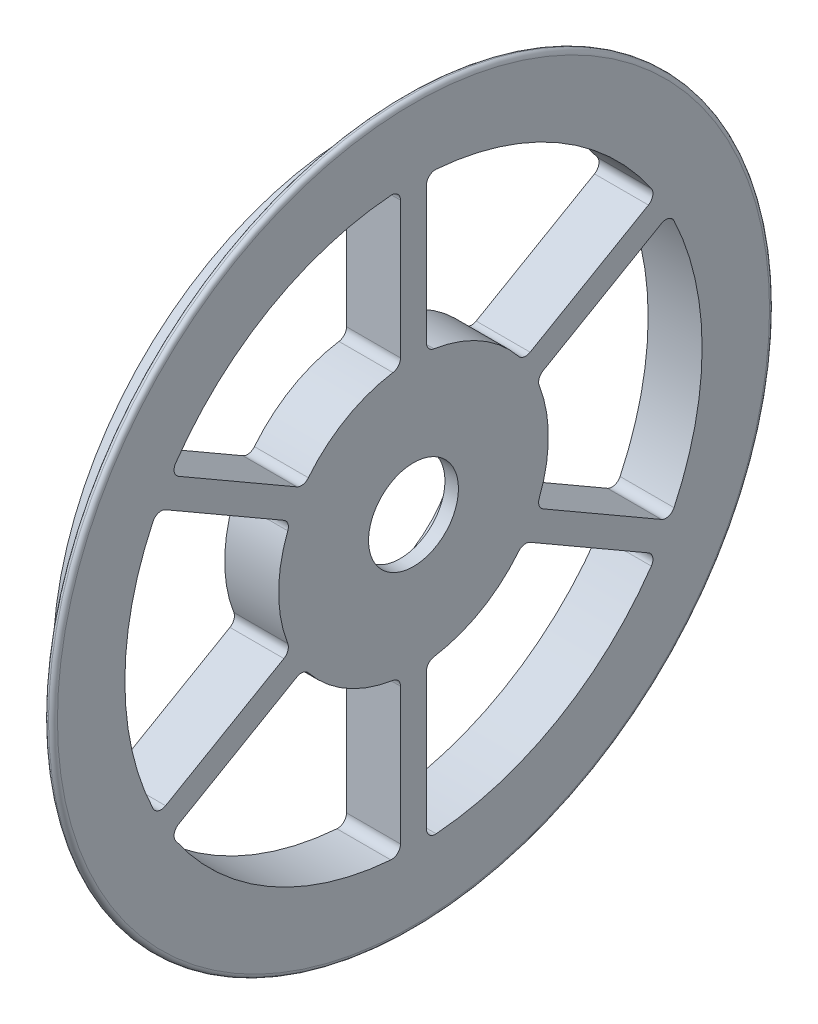
SolidWorks part; units mm, degrees
ref_plane "Front Plane" through (0, 0, 0) normal (0, 0, 1) x (1, 0, 0)
ref_plane "Top Plane" through (0, 0, 0) normal (0, 1, 0) x (1, 0, 0)
ref_plane "Right Plane" through (0, 0, 0) normal (1, 0, 0) x (0, 0, -1)
sketch "Sketch1" plane through (0, 0, 0) normal (0, 0, 1) x (1, 0, 0)
  line L2 (-3, 0) -> (-3, 38.05)
  line L5 (-3, 38.05) -> (2, 38.05)
  line L14 (2, 38.05) -> (2, 40.1)
  line L15 (2, 40.1) -> (3, 40.1)
  line L16 (3, 40.1) -> (3, 0)
  line L17 (3, 0) -> (-3, 0)
  dimension "D3" = 40.1
  dimension "D1" = 1
  dimension "D2" = 5
  dimension "D4" = 38.05
revolve "Revolve2" add sketch "Sketch1" angle 360 about L17
sketch "Sketch2" plane through (3, 0, 0) normal (-1, 0, 0) x (0, 0, 1)
  line L0 (0, 0) -> (13.6518, 0) construction
  line L1 (14.4156, 6.6562) -> (27.5718, 14.2519)
  line L2 (13.6518, 6.2152) -> (13.6518, -6.2152) construction
  line L3 (14.4156, -6.6562) -> (27.5718, -14.2519)
  line L4 (28.493, 14.7838) -> (28.493, -14.7838) construction
  line L5 (2.8868, 0) -> (13.6518, 6.2152) construction
  line L6 (2.8868, 0) -> (1.4434, 2.5) construction
  line L7 (1.4434, 2.5) -> (-1.4434, 2.5) construction
  line L8 (-1.4434, 2.5) -> (-2.8868, 0) construction
  line L9 (-2.8868, 0) -> (-1.4434, -2.5) construction
  line L10 (-1.4434, -2.5) -> (1.4434, -2.5) construction
  line L11 (1.4434, -2.5) -> (2.8868, 0) construction
  line L12 (13.6518, 0) -> (28.493, 0) construction
  line L13 (13.6518, -6.2152) -> (2.8868, 0) construction
  line L14 (12.9722, -9.1562) -> (26.1285, -16.7519)
  line L15 (1.4434, -15.8123) -> (1.4434, -31.0039)
  line L16 (-1.4434, -15.8123) -> (-1.4434, -31.0039)
  line L17 (-12.9722, -9.1562) -> (-26.1285, -16.7519)
  line L18 (-14.4156, -6.6562) -> (-27.5718, -14.2519)
  line L19 (-14.4156, 6.6562) -> (-27.5718, 14.2519)
  line L20 (-12.9722, 9.1562) -> (-26.1285, 16.7519)
  line L21 (-1.4434, 15.8123) -> (-1.4434, 31.0039)
  line L22 (1.4434, 15.8123) -> (1.4434, 31.0039)
  line L23 (12.9722, 9.1562) -> (26.1285, 16.7519)
  arc A0 (28.9745, 13.8163) -> (28.9745, -13.8163) centre (0, 0) cw
  circle A2 centre (0, 0) radius 2.5 construction
  arc A3 (13.9833, 5.4283) -> (13.9833, -5.4283) centre (0, 0) cw
  arc A4 (13.9833, -5.4283) -> (14.4156, -6.6562) centre (14.9156, -5.7901) ccw
  arc A5 (14.4156, 6.6562) -> (13.9833, 5.4283) centre (14.9156, 5.7901) ccw
  arc A6 (27.5718, -14.2519) -> (28.9745, -13.8163) centre (28.0718, -13.3859) ccw
  arc A7 (28.9745, 13.8163) -> (27.5718, 14.2519) centre (28.0718, 13.3859) ccw
  arc A8 (26.4525, -18.1845) -> (26.1285, -16.7519) centre (25.6285, -17.618) ccw
  arc A9 (26.4525, -18.1845) -> (2.5219, -32.0008) centre (0, 0) cw
  arc A10 (1.4434, -31.0039) -> (2.5219, -32.0008) centre (2.4434, -31.0039) ccw
  arc A11 (2.2907, -14.8241) -> (1.4434, -15.8123) centre (2.4434, -15.8123) ccw
  arc A12 (11.6927, -9.3958) -> (2.2907, -14.8241) centre (0, 0) cw
  arc A13 (12.9722, -9.1562) -> (11.6927, -9.3958) centre (12.4722, -10.0222) ccw
  arc A14 (-2.5219, -32.0008) -> (-1.4434, -31.0039) centre (-2.4434, -31.0039) ccw
  arc A15 (-2.5219, -32.0008) -> (-26.4525, -18.1845) centre (0, 0) cw
  arc A16 (-26.1285, -16.7519) -> (-26.4525, -18.1845) centre (-25.6285, -17.618) ccw
  arc A17 (-11.6927, -9.3958) -> (-12.9722, -9.1562) centre (-12.4722, -10.0222) ccw
  arc A18 (-2.2907, -14.8241) -> (-11.6927, -9.3958) centre (0, 0) cw
  arc A19 (-1.4434, -15.8123) -> (-2.2907, -14.8241) centre (-2.4434, -15.8123) ccw
  arc A20 (-28.9745, -13.8163) -> (-27.5718, -14.2519) centre (-28.0718, -13.3859) ccw
  arc A21 (-28.9745, -13.8163) -> (-28.9745, 13.8163) centre (0, 0) cw
  arc A22 (-27.5718, 14.2519) -> (-28.9745, 13.8163) centre (-28.0718, 13.3859) ccw
  arc A23 (-13.9833, 5.4283) -> (-14.4156, 6.6562) centre (-14.9156, 5.7901) ccw
  arc A24 (-13.9833, -5.4283) -> (-13.9833, 5.4283) centre (0, 0) cw
  arc A25 (-14.4156, -6.6562) -> (-13.9833, -5.4283) centre (-14.9156, -5.7901) ccw
  arc A26 (-26.4525, 18.1845) -> (-26.1285, 16.7519) centre (-25.6285, 17.618) ccw
  arc A27 (-26.4525, 18.1845) -> (-2.5219, 32.0008) centre (0, 0) cw
  arc A28 (-1.4434, 31.0039) -> (-2.5219, 32.0008) centre (-2.4434, 31.0039) ccw
  arc A29 (-2.2907, 14.8241) -> (-1.4434, 15.8123) centre (-2.4434, 15.8123) ccw
  arc A30 (-11.6927, 9.3958) -> (-2.2907, 14.8241) centre (0, 0) cw
  arc A31 (-12.9722, 9.1562) -> (-11.6927, 9.3958) centre (-12.4722, 10.0222) ccw
  arc A32 (2.5219, 32.0008) -> (1.4434, 31.0039) centre (2.4434, 31.0039) ccw
  arc A33 (2.5219, 32.0008) -> (26.4525, 18.1845) centre (0, 0) cw
  arc A34 (26.1285, 16.7519) -> (26.4525, 18.1845) centre (25.6285, 17.618) ccw
  arc A35 (11.6927, 9.3958) -> (12.9722, 9.1562) centre (12.4722, 10.0222) ccw
  arc A36 (2.2907, 14.8241) -> (11.6927, 9.3958) centre (0, 0) cw
  arc A37 (1.4434, 15.8123) -> (2.2907, 14.8241) centre (2.4434, 15.8123) ccw
  circle A39 centre (0, 0) radius 40.1 construction
  point P92 (0, 0)
  dimension "D5" = 5
  dimension "D2" = 15
  dimension "D3" = 1
  dimension "D1" = 30
  dimension "D4" = 8
  dimension "D6" = 6
extrude "Cut-Extrude2" cut sketch "Sketch2" along normal through all
fillet "Fillet1" radius 0.5 2 edges at (3, 0, -40.1) (2, 0, -40.1)
sketch "Sketch7" plane through (3, 0, 0) normal (1, 0, 0) x (0, 0, -1)
  circle A0 centre (0, 0) radius 5
  dimension "D1" = 10
extrude "Cut-Extrude5" cut sketch "Sketch7" against normal through all both and the other way through all
sketch "Sketch9" plane through (-3, 0, 0) normal (-1, 0, 0) x (0, 0, 1)
  circle A0 centre (0, 0) radius 34.1
  circle A1 centre (0, 0) radius 50
  dimension "D1" = 68.2
  dimension "D2" = 100
extrude "Cut-Extrude6" cut sketch "Sketch9" against normal offset from surface (4 mm away) 1 up to face at (2, 0, 39.6)
sketch "Sketch8" plane through (-3, 0, 0) normal (1, 0, 0) x (0, 0, -1)
  circle A0 centre (0, 0) radius 11.025
  dimension "D1" = 22.05
extrude "Cut-Extrude7" cut sketch "Sketch8" along normal offset from surface (4.5 mm away) 1.5 up to face at (3, 0, -5)
equation "\"SpokeWidth\"= 5"
equation "\"D5@Sketch2\" = \"SpokeWidth\""
equation "\"HubDiameter\"= 30"
equation "\"D2@Sketch2\"=\"HubDiameter\"/2"
equation "\"PulleyDiameter\"= 3in"
equation "\"PulleyWidth\"= 3.45in"
equation "\"RimWidth\"= 8"
equation "\"D4@Sketch2\"=\"RimWidth\""
